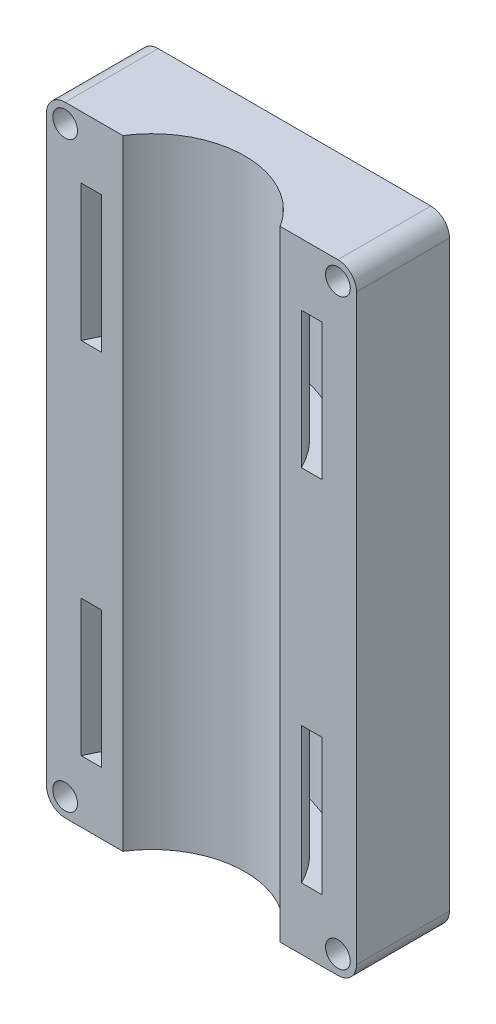
SolidWorks part; units mm, degrees
ref_plane "Front Plane" through (0, 0, 0) normal (0, 0, 1) x (1, 0, 0)
ref_plane "Top Plane" through (0, 0, 0) normal (0, 1, 0) x (1, 0, 0)
ref_plane "Right Plane" through (0, 0, 0) normal (1, 0, 0) x (0, 0, -1)
sketch "Sketch1" plane through (0, 0, 0) normal (0, 0, 1) x (1, 0, 0)
  line L1 (-22.007, -50.0002) -> (21.993, -50.0002)
  line L2 (-25.007, -47.0002) -> (-25.007, 46.9998)
  line L3 (-22.007, 49.9998) -> (21.993, 49.9998)
  line L4 (24.993, -47.0002) -> (24.993, 46.9998)
  line L5 (-25.007, -50.0002) -> (24.993, 49.9998) construction
  line L6 (-25.007, 49.9998) -> (24.993, -50.0002) construction
  line L7 (-22.007, -47.0002) -> (21.993, -47.0002)
  line L8 (-22.007, -47.0002) -> (-22.007, 46.9998)
  line L9 (-22.007, 46.9998) -> (21.993, 46.9998)
  line L10 (21.993, -47.0002) -> (21.993, 46.9998)
  line L11 (-22.007, -47.0002) -> (21.993, 46.9998) construction
  line L12 (-22.007, 46.9998) -> (21.993, -47.0002) construction
  arc A0 (-22.007, -50.0002) -> (-25.007, -47.0002) centre (-22.007, -47.0002) cw
  arc A1 (21.993, -50.0002) -> (24.993, -47.0002) centre (21.993, -47.0002) ccw
  arc A2 (21.993, 49.9998) -> (24.993, 46.9998) centre (21.993, 46.9998) cw
  arc A3 (-25.007, 46.9998) -> (-22.007, 49.9998) centre (-22.007, 46.9998) cw
  circle A4 centre (-22.007, 46.9998) radius 2
  circle A5 centre (21.993, 46.9998) radius 2
  circle A6 centre (21.993, -47.0002) radius 2
  circle A7 centre (-22.007, -47.0002) radius 2
  circle A8 centre (-22.007, 46.9998) radius 3
  circle A9 centre (21.993, 46.9998) radius 3
  circle A10 centre (21.993, -47.0002) radius 3
  circle A11 centre (-22.007, -47.0002) radius 3
  point P0 (-0.007, -0.0002)
  point P26 (-0.007, -0.0002)
  dimension "D3" = 3
  dimension "D4" = 4
  dimension "D1" = 100
  dimension "D2" = 50
extrude "Boss-Extrude1" add sketch "Sketch1" along normal blind 15 contours L10 A5 L9 | L9 A5 L10 | L9 A4 L8 | L8 A4 L9 | L7 A6 L10 | L10 A6 L7 | L8 A7 L7 | L7 A7 L8 | L4 A2 L3 A3 L2 A0 L1 A1 region at (-22.29, -47.2832, 0) region at (-21.1582, -46.1514, 0) region at (21.1441, -46.1514, 0) region at (22.2759, -47.2832, 0) region at (-22.29, 47.2827, 0) region at (-21.1582, 46.151, 0) region at (21.1441, 46.151, 0) region at (22.2759, 47.2827, 0)
sketch "Sketch2" plane through (0, 49.9998, 0) normal (0, 1, 0) x (1, 0, 0)
  line L0 (-22.007, -15) -> (21.993, -15) construction
  line L1 (-19.4165, -15) -> (19.4165, -15)
  arc A0 (12.6886, -15) -> (-12.6886, -15) centre (0, -23) ccw
  arc A1 (16.1245, -15) -> (-16.1245, -15) centre (0, -23) ccw
  arc A2 (19.4165, -15) -> (-19.4165, -15) centre (0, -23) ccw
  line M3 (-22.007, -15) -> (21.993, -15)
  dimension "D2" = 30
  dimension "D3" = 3
  dimension "D4" = 3
  dimension "D1" = 8
extrude "Cut-Extrude1" cut sketch "Sketch2" against normal through all contours L1 A0 region at (0, 49.9998, 12.1352)
extrude "Cut-Extrude2" cut sketch "Sketch2<4>" against normal blind 22 from offset 10 contours L1 A2 A1 M3 region at (0, 49.9998, 2.4095) offset against normal yes
sketch "Sketch2<4>" plane through (0, 49.9998, 0) normal (0, 1, 0) x (1, 0, 0) same geometry as "Sketch2"
extrude "Cut-Extrude3" cut sketch "Sketch2<5>" against normal blind 22 from offset 68 contours L1 A2 A1 M3 region at (0, 49.9998, 2.4095) offset against normal yes
sketch "Sketch2<5>" plane through (0, 49.9998, 0) normal (0, 1, 0) x (1, 0, 0) same geometry as "Sketch2"
